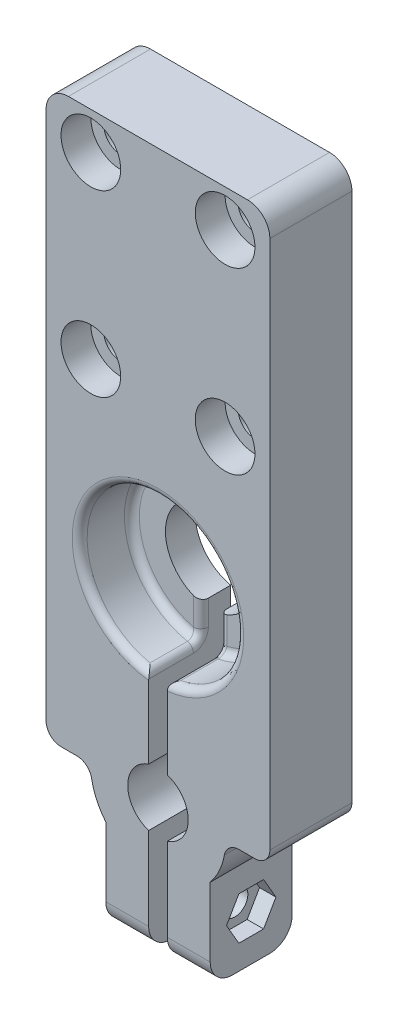
SolidWorks part; units mm, degrees
material "ABS"
ref_plane "Front Plane" through (0, 0, 0) normal (0, 0, 1) x (1, 0, 0)
ref_plane "Top Plane" through (0, 0, 0) normal (0, 1, 0) x (1, 0, 0)
ref_plane "Right Plane" through (0, 0, 0) normal (1, 0, 0) x (0, 0, -1)
sketch "Sketch2" plane through (0, 0, 0) normal (0, 0, 1) x (1, 0, 0)
  line L1 (-15, -17) -> (15, -17)
  line L2 (-15, -17) -> (-15, 17)
  line L3 (-15, 17) -> (15, 17)
  line L4 (15, -17) -> (15, 17)
  line L5 (-15, -17) -> (15, 17) construction
  line L6 (-15, 17) -> (15, -17) construction
  line L7 (-9, -12) -> (9, -12) construction
  line L8 (-9, -12) -> (-9, 12) construction
  line L9 (-9, 12) -> (9, 12) construction
  line L10 (9, -12) -> (9, 12) construction
  line L11 (-9, -12) -> (9, 12) construction
  line L12 (-9, 12) -> (9, -12) construction
  point P0 (0, 0)
  point P6 (0, 0)
  dimension "D1" = 34
  dimension "D2" = 30
  dimension "D3" = 5
  dimension "D4" = 6
extrude "Boss-Extrude1" add sketch "Sketch2" along normal blind 11 contours L3 L4 L1 L2
hole_wizard "CBORE for M4 SHCS1" positions "Sketch3" profile "Sketch4" counterbore size "M4" standard "ANSI Metric" end condition through all
sketch "Sketch3" plane through (0, 0, 11) normal (0, 0, 1) x (1, 0, 0)
  point P0 (-9, 12)
  point P3 (9, 12)
  point P6 (-9, -12)
  point P9 (9, -12)
sketch "Sketch4" plane through (-9, 12, 11) normal (1, 0, 0) x (0, -1, 0)
  line L0 (0, 0) -> (0, 11)
  line L1 (0, 11) -> (2.25, 11)
  line L3 (2.25, 11) -> (2.25, 4)
  line L4 (2.25, 4) -> (4, 4)
  line L5 (4, 4) -> (4, 0)
  line L7 (4, 0) -> (0, 0)
  line L11 (0, -6.35) -> (0, 107.95) construction
  dimension "Thru Hole Dia." = 4.5
  dimension "Thru Hole Depth" = 11
  dimension "C'Bore Dia." = 8
  dimension "C'Bore Depth" = 4
sketch "Sketch6" plane through (0, 0, 0) normal (0, 0, 1) x (1, 0, 0)
  line L0 (15, -17) -> (15, 17) construction
  line L1 (-15, -17) -> (15, -17)
  line L2 (-15, -17) -> (-15, -77)
  line L3 (-15, -77) -> (15, -77)
  line L4 (15, -17) -> (15, -77)
  circle A0 centre (0, -34) radius 10.5
  circle A1 centre (0, -59) radius 4.05
  dimension "D1" = 21
  dimension "D3" = 8.1
  dimension "D2" = 59
  dimension "D4" = 60
  dimension "D5" = 34
extrude "Boss-Extrude2" add sketch "Sketch6" along normal up to surface (11 mm away) up to face at (-5, 12, 11)
sketch "Sketch8" plane through (0, 0, 0) normal (0, 0, 1) x (1, 0, 0)
  circle A0 centre (0, -34) radius 6
  circle A1 centre (0, -34) radius 10.5
  circle A2 centre (0, -34) radius 10.5 construction
  dimension "D1" = 12
extrude "Boss-Extrude3" add sketch "Sketch8" along normal blind 4 from surface starting at face at (-6.75, 12, 0)
sketch "Sketch7" plane through (0, 0, 11) normal (0, 0, 1) x (1, 0, 0)
  line L0 (-1.25, -77) -> (-1.25, 0)
  line L5 (-7, -64.7361) -> (-7, -77)
  line L6 (-1.25, -77) -> (1.25, -77)
  line L7 (7, -64.7361) -> (7, -77)
  line L8 (-1.25, 0) -> (1.25, 0)
  line L9 (-15, 17) -> (-15, -77)
  line L10 (-15, -77) -> (15, -77)
  line L11 (15, -77) -> (15, 17)
  line L12 (15, 17) -> (-15, 17)
  line L13 (-15, 17) -> (-15, -77)
  line L15 (15, -77) -> (15, 17)
  line L16 (15, 17) -> (-15, 17)
  line L17 (-9.05, -59) -> (-15, -59)
  line L18 (9.05, -59) -> (15, -59)
  line L19 (1.25, -77) -> (1.25, 0)
  line L20 (-1.25, -77) -> (1.25, 0) construction
  line L21 (-7, -64.7361) -> (7, -64.7361) construction
  line L22 (-1.25, 0) -> (1.25, -77) construction
  line L26 (-15, -77) -> (15, -77)
  circle A0 centre (0, -34) radius 10.5 construction
  circle A1 centre (0, -34) radius 10.5
  circle A4 centre (0, -59) radius 9.05
  circle A5 centre (0, -59) radius 9.05
  point P0 (0, 0)
  point P1 (0, -38.5)
  line M10 (-15, -77) -> (15, -77)
  line M11 (15, -77) -> (15, 17)
  circle M13 centre (0, -59) radius 4.05
  circle M14 centre (0, -34) radius 10.5
  dimension "D3" = 14
  dimension "D4" = 2.5
  dimension "D1" = 0
  dimension "D2" = 5
extrude "Cut-Extrude1" cut sketch "Sketch7" against normal through all and the other way through all contours A5 L17 L13 L5 M10 | A5 L7 L18 M10 M11 | A5 L0 L19 M10 | L19 A5 L0 M13 | A5 L19 L0 M14 | L19 L0 M14 | L0 A5 L19 M13 region at (0, -72.5105, 11) region at (0, -65.5027, 11) region at (-11.1874, -68.4026, 11) region at (11.1874, -68.4026, 11) region at (0, -52.4973, 11) region at (0, -47.227, 11) region at (0, -34, 11)
fillet "Fillet2" radius 2 4 edges at (15, -59, 5.5) (-15, -59, 5.5) (-9.05, -59, 5.5) (9.05, -59, 5.5)
fillet "Fillet3" radius 1 12 edges at (0, -23.5, 0) (-1.25, -23.5747, 2) (-10.5, -34, 4) (-1.25, -44.4253, 7.5) (0, -23.5, 11) (1.25, -44.4253, 7.5) (10.5, -34, 4) (1.25, -23.5747, 2) (1.25, -42.1468, 4) (1.25, -25.8532, 0) (-1.25, -25.8532, 0) (-1.25, -42.1468, 4)
sketch "Sketch9" plane through (7, 0, 0) normal (1, 0, 0) x (0, 0, -1)
  line L0 (-11, -64.7361) -> (-11, -77) construction
  line L1 (-11, -77) -> (-11, -64.7361) construction
  line L2 (0, -77) -> (-11, -77) construction
  line L4 (-2.186, -70.868) -> (-3.843, -67.998)
  line L5 (-3.843, -67.998) -> (-7.157, -67.998)
  line L6 (-7.157, -67.998) -> (-8.814, -70.868)
  line L7 (-8.814, -70.868) -> (-7.157, -73.738)
  line L8 (-7.157, -73.738) -> (-3.843, -73.738)
  line L9 (-3.843, -73.738) -> (-2.186, -70.868)
  circle A0 centre (-5.5, -70.868) radius 1.75
  circle A1 centre (-5.5, -70.868) radius 2.87 construction
  point P7 (-11, -70.868)
  point P11 (-5.5, -77)
  dimension "D1" = 3.5
  dimension "D2" = 5.74
extrude "Cut-Extrude2" cut sketch "Sketch9" against normal through all contours A0
extrude "Cut-Extrude3" cut sketch "Sketch9<3>" against normal blind 2.2
sketch "Sketch9<3>" plane through (7, 0, 0) normal (1, 0, 0) x (0, 0, -1) same geometry as "Sketch9"
fillet "Fillet4" radius 3 6 edges at (-15, 17, 5.5) (15, 17, 5.5) (4.125, -77, 0) (4.125, -77, 11) (-4.125, -77, 11) (-4.125, -77, 0)
